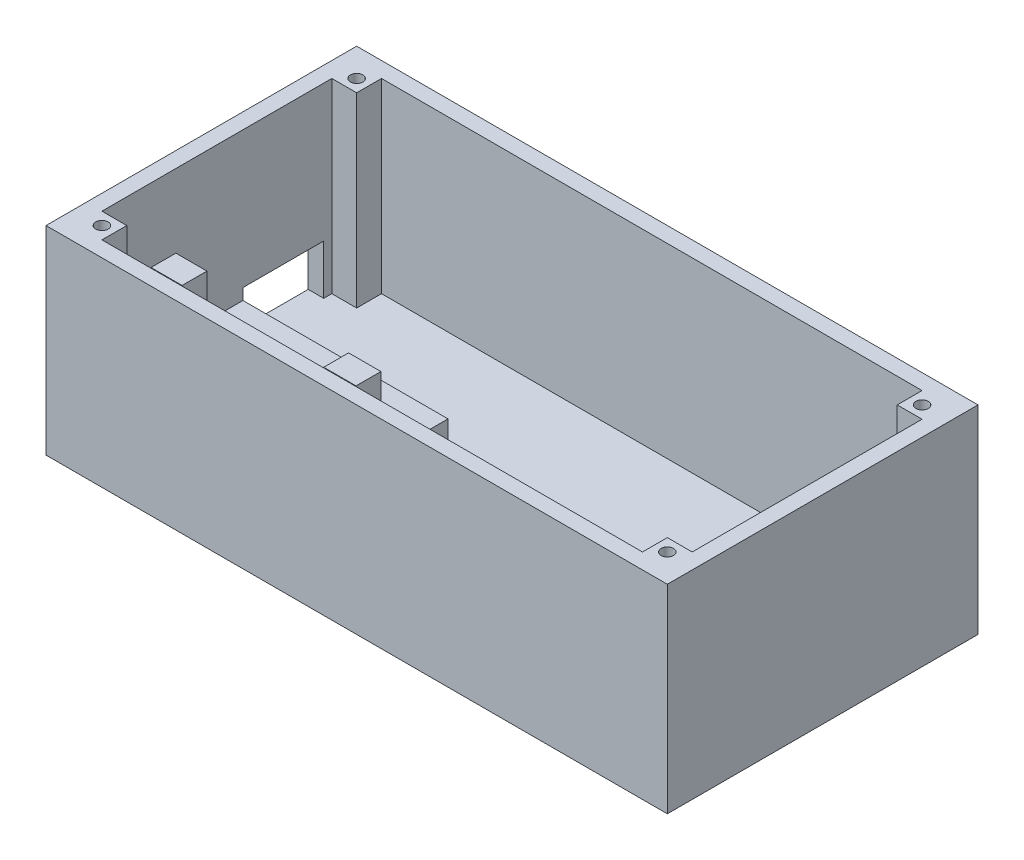
SolidWorks part; units mm, degrees
ref_plane "Front Plane" through (0, 0, 0) normal (0, 0, 1) x (1, 0, 0)
ref_plane "Top Plane" through (0, 0, 0) normal (0, 1, 0) x (1, 0, 0)
ref_plane "Right Plane" through (0, 0, 0) normal (1, 0, 0) x (0, 0, -1)
sketch "Sketch1" plane through (0, 0, 0) normal (0, 1, 0) x (1, 0, 0)
  line L1 (0, 0) -> (100, 0)
  line L2 (0, 0) -> (0, 50)
  line L3 (0, 50) -> (100, 50)
  line L4 (100, 0) -> (100, 50)
  dimension "D1" = 100
  dimension "D2" = 50
extrude "Boss-Extrude1" add sketch "Sketch1" along normal blind 2
sketch "Sketch3" plane through (0, 2, 0) normal (0, 1, 0) x (1, 0, 0)
  line L1 (0, 50) -> (100, 50)
  line L2 (0, 50) -> (0, 0)
  line L3 (0, 0) -> (100, 0)
  line L4 (100, 50) -> (100, 0)
  line L5 (6.5, 47.5) -> (93.5, 47.5)
  line L6 (2.5, 43.5) -> (2.5, 6.5)
  line L7 (6.5, 2.5) -> (93.5, 2.5)
  line L8 (97.5, 43.5) -> (97.5, 6.5)
  line L11 (2.5, 43.5) -> (6.5, 43.5)
  line L12 (6.5, 47.5) -> (6.5, 43.5)
  line L14 (97.5, 43.5) -> (93.5, 43.5)
  line L15 (93.5, 47.5) -> (93.5, 43.5)
  line L16 (97.5, 6.5) -> (93.5, 6.5)
  line L17 (93.5, 2.5) -> (93.5, 6.5)
  line L18 (6.5, 2.5) -> (6.5, 6.5)
  line L19 (2.5, 6.5) -> (6.5, 6.5)
  line L20 (6.5, 47.5) -> (2.5, 43.5) construction
  circle A0 centre (4.5, 45.5) radius 1
  circle A1 centre (95.5, 45.5) radius 1
  circle A2 centre (95.5, 4.5) radius 1
  circle A3 centre (4.5, 4.5) radius 1
  dimension "D7" = 2
  dimension "D8" = 2
  dimension "D1" = 2.5
  dimension "D2" = 2.5
  dimension "D3" = 2.5
  dimension "D4" = 2.5
  dimension "D5" = 4
  dimension "D6" = 4
  dimension "D9" = 2
extrude "Boss-Extrude2" add sketch "Sketch3" along normal blind 30
sketch "Sketch4" plane through (0, 2, 0) normal (0, 1, 0) x (1, 0, 0)
  line L2 (2.5, 43.5) -> (2.5, 6.5) construction
  line L3 (2.5, 29.2) -> (35.5, 29.2)
  line L4 (2.5, 29.2) -> (2.5, 6.5)
  line L5 (6.5, 2.5) -> (35.5, 2.5)
  line L6 (35.5, 29.2) -> (35.5, 2.5)
  line L7 (6.5, 2.5) -> (93.5, 2.5) construction
  line L8 (2.5, 6.5) -> (6.5, 6.5)
  line L9 (6.5, 6.5) -> (6.5, 2.5)
  dimension "D1" = 22.7
  dimension "D4" = 33
extrude "Boss-Extrude3" add sketch "Sketch4" along normal blind 6.2
sketch "Sketch5" plane through (0, 2, 0) normal (0, 1, 0) x (1, 0, 0)
  line L0 (0, 0) -> (0, 29.9) construction
  line L1 (0, 50) -> (0, 0) construction
  point P5 (0, 26.7)
  point P6 (0, 15.9)
  dimension "D1" = 29.9
  dimension "D2" = 26.7
  dimension "D3" = 15.9
sketch "Sketch6" plane through (0, 8.2, 0) normal (0, 1, 0) x (1, 0, 0)
  line L0 (2.5, 43.5) -> (2.5, 6.5) construction
  line L1 (2.5, 18.4) -> (7.5, 18.4)
  line L2 (2.5, 18.4) -> (2.5, 14.4)
  line L3 (2.5, 14.4) -> (7.5, 14.4)
  line L4 (7.5, 18.4) -> (7.5, 14.4)
  line L5 (35.5, 2.5) -> (35.5, 29.2) construction
  line L6 (30.3, 18.4) -> (35.5, 18.4)
  line L7 (30.3, 18.4) -> (30.3, 14.4)
  line L8 (30.3, 14.4) -> (35.5, 14.4)
  line L9 (35.5, 18.4) -> (35.5, 14.4)
  dimension "D1" = 5
  dimension "D2" = 4
  dimension "D3" = 22.8
  dimension "D4" = 18.4
extrude "Boss-Extrude4" add sketch "Sketch6" along normal blind 12
sketch "Sketch7" plane through (2.5, 0, 0) normal (1, 0, 0) x (0, 0, -1)
  line L1 (29.2, 2) -> (42.2, 2)
  line L2 (29.2, 2) -> (29.2, 10)
  line L3 (29.2, 10) -> (42.2, 10)
  line L4 (42.2, 2) -> (42.2, 10)
  dimension "D1" = 13
  dimension "D2" = 8
extrude "Cut-Extrude1" cut sketch "Sketch7" against normal blind 15
sketch "Sketch8" plane through (97.5, 0, 0) normal (-1, 0, 0) x (0, 0, 1)
  line L0 (-6.5, 2) -> (-43.5, 2) construction
  line L1 (-27.5, 2) -> (-15.5, 2)
  line L2 (-27.5, 2) -> (-27.5, 9)
  line L3 (-27.5, 9) -> (-15.5, 9)
  line L4 (-15.5, 2) -> (-15.5, 9)
  line L5 (-6.5, 32) -> (-6.5, 2) construction
  point P8 (-15.5, 5.5)
  dimension "D1" = 9
  dimension "D2" = 12
  dimension "D3" = 7
